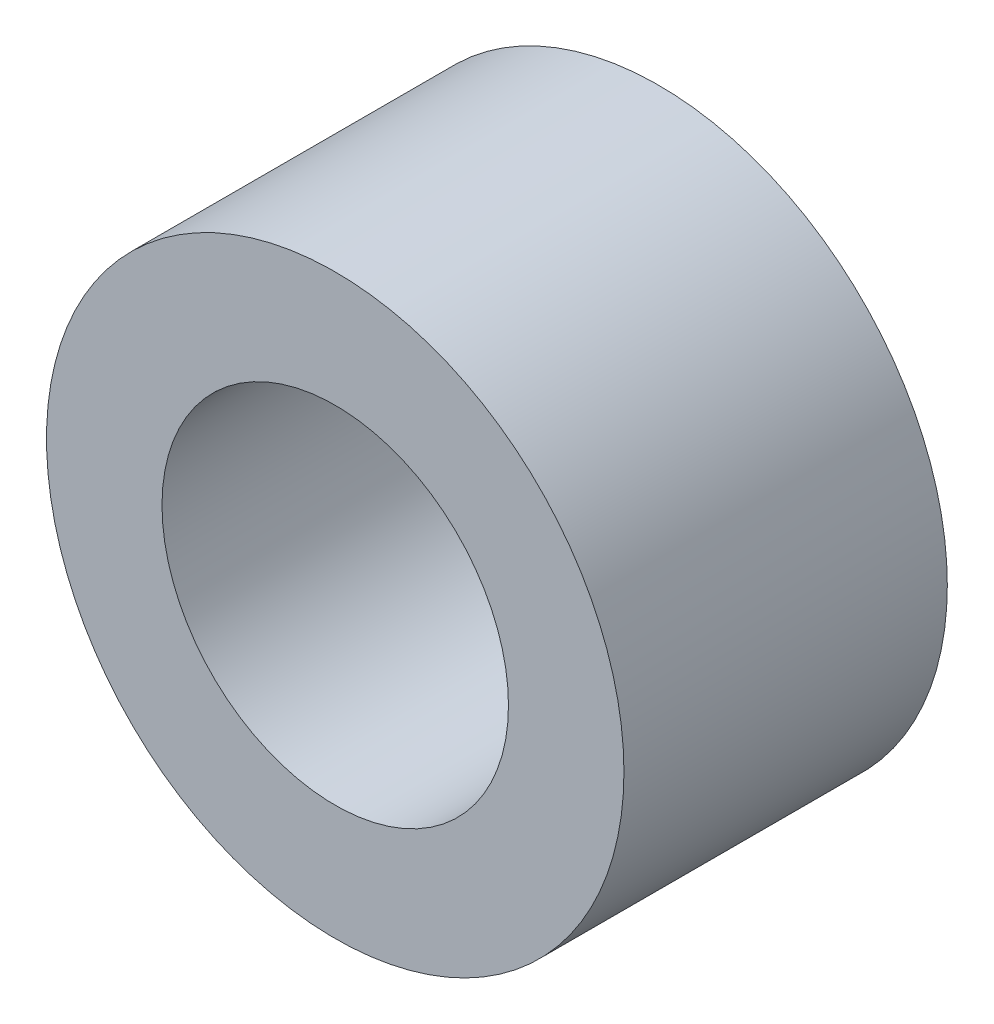
SolidWorks part; units mm, degrees
ref_plane "前视基准面" through (0, 0, 0) normal (0, 0, 1) x (1, 0, 0)
ref_plane "上视基准面" through (0, 0, 0) normal (0, 1, 0) x (1, 0, 0)
ref_plane "右视基准面" through (0, 0, 0) normal (1, 0, 0) x (0, 0, -1)
sketch "草图1" plane through (0, 0, 0) normal (0, 0, 1) x (1, 0, 0)
  circle A0 centre (0, 0) radius 1.5
  circle A1 centre (0, 0) radius 2.5
extrude "凸台-拉伸1" add sketch "草图1" along normal blind 2.8
